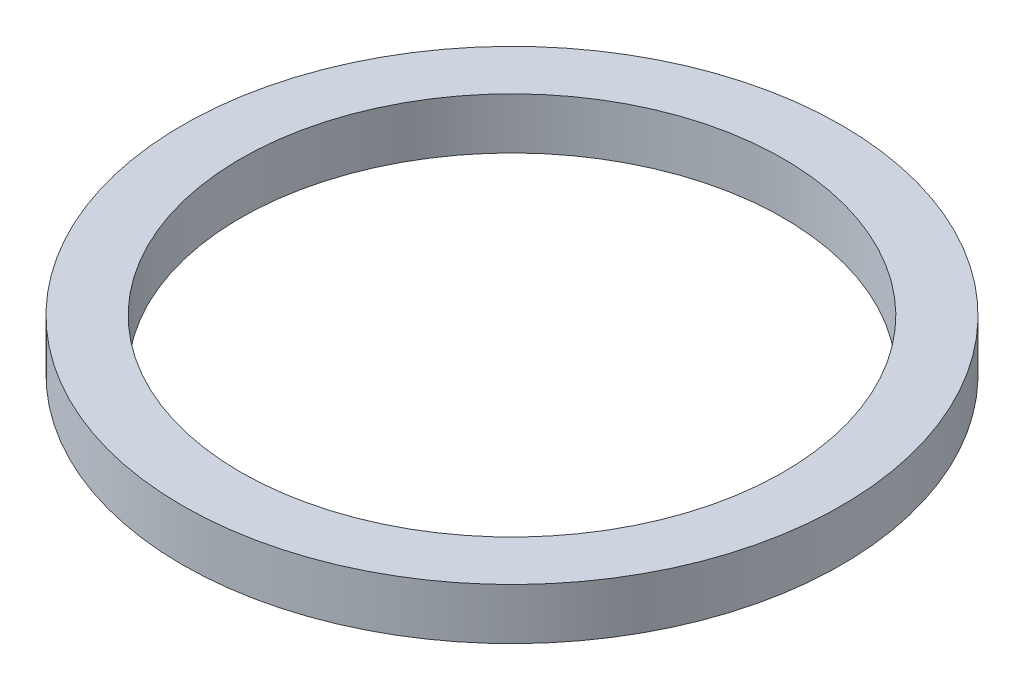
SolidWorks part; units mm, degrees
material "Pine"
ref_plane "Front Plane" through (0, 0, 0) normal (0, 0, 1) x (1, 0, 0)
ref_plane "Top Plane" through (0, 0, 0) normal (0, 1, 0) x (1, 0, 0)
ref_plane "Right Plane" through (0, 0, 0) normal (1, 0, 0) x (0, 0, -1)
sketch "Sketch1" plane through (0, 0, 0) normal (0, 1, 0) x (1, 0, 0)
  circle A0 centre (0, 0) radius 15.9
  circle A1 centre (0, 0) radius 19.305
  dimension "D1" = 31.8
  dimension "D2" = 38.61
extrude "Boss-Extrude1" add sketch "Sketch1" along normal blind 3
